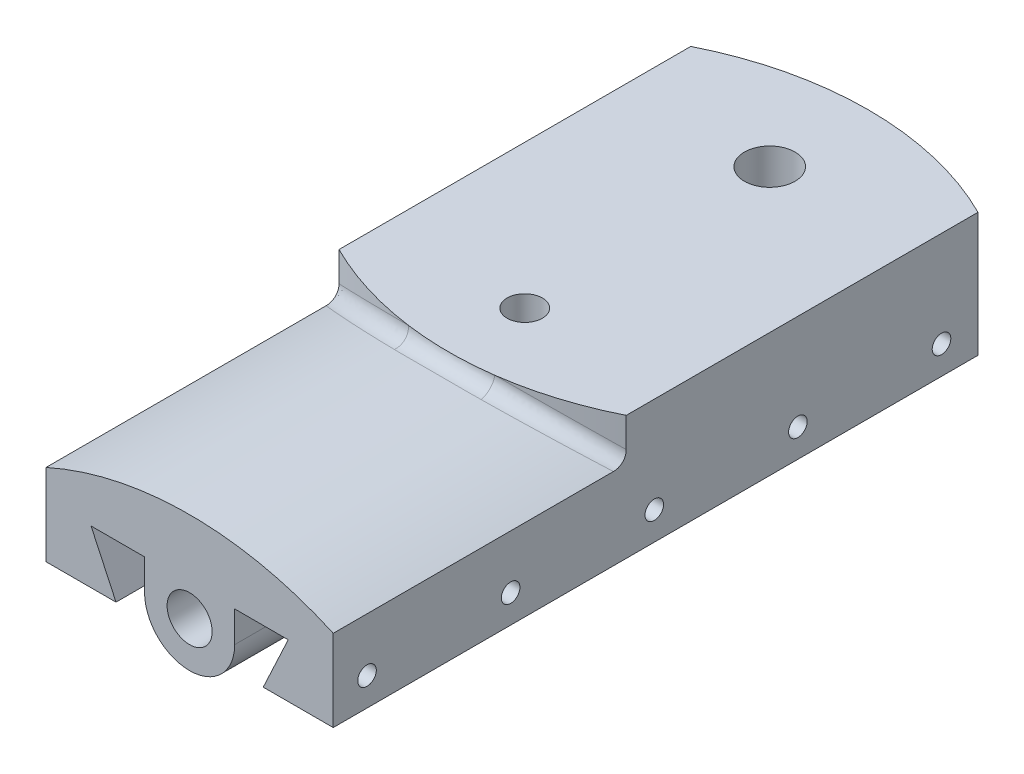
SolidWorks part; units mm, degrees
ref_plane "Ön Düzlem" through (0, 0, 0) normal (0, 0, 1) x (1, 0, 0)
ref_plane "Üst Düzlem" through (0, 0, 0) normal (0, 1, 0) x (1, 0, 0)
ref_plane "Sağ Düzlem" through (0, 0, 0) normal (1, 0, 0) x (0, 0, -1)
sketch "Çizim2" plane through (0, 0, 0) normal (0, 0, 1) x (1, 0, 0)
  line L0 (0, 0) -> (0, 44) construction
  line L1 (-51, 44) -> (51, 44)
  line L2 (51, 44) -> (51, 0)
  line L3 (51, 0) -> (26.1402, 0)
  line L4 (26.1402, 0) -> (35, 19)
  line L5 (35, 19) -> (16, 19)
  line L6 (16, 19) -> (16, 8)
  line L7 (0, 0) -> (0, -8) construction
  line L8 (-16, 19) -> (-16, 8)
  line L9 (-35, 19) -> (-16, 19)
  line L10 (-26.1402, 0) -> (-35, 19)
  line L11 (-51, 44) -> (-51, 0)
  line L12 (-51, 0) -> (-26.1402, 0)
  arc A0 (-16, 8) -> (16, 8) centre (0, 8) ccw
  circle A1 centre (0, 8) radius 8
  dimension "D8" = 16
  dimension "D1" = 44
  dimension "D2" = 51
  dimension "D3" = 35
  dimension "D4" = 65
  dimension "D5" = 19
  dimension "D6" = 16
  dimension "D7" = 11
extrude "Yükseklik-Ekstrüzyon1" add sketch "Çizim2" along normal mid plane 241
sketch "Çizim3" plane through (0, 0, 120.5) normal (0, 0, 1) x (1, 0, 0)
  line L0 (-51, 44) -> (-51, 0) construction
  line L1 (51, 0) -> (51, 44) construction
  line L2 (26.1402, 0) -> (51, 0) construction
  line L3 (-51, 0) -> (-26.1402, 0) construction
  line L4 (-51, 29) -> (-51, 44)
  line L5 (-51, 44) -> (51, 44)
  line L6 (51, 44) -> (51, 29)
  arc A0 (-51, 29) -> (51, 29) centre (0, -83.7273) cw
  point P11 (0, 40)
  dimension "D1" = 29
  dimension "D2" = 40
extrude "Kes-Ekstrüzyon2" cut sketch "Çizim3" against normal blind 92
sketch "Çizim4" plane through (0, 44, 0) normal (0, 1, 0) x (1, 0, 0)
  line L0 (0, 120.5) -> (0, 85.5) construction
  line L1 (51, 120.5) -> (-51, 120.5) construction
  line L2 (-51, -28.5) -> (-51, 0)
  line L3 (-51, -28.5) -> (-51, 120.5) construction
  line L4 (-51, -28.5) -> (24.9037, -28.5)
  line L5 (51, -28.5) -> (-51, -28.5) construction
  line L6 (24.9037, -28.5) -> (51, -28.5)
  line L7 (-51, -28.5) -> (51, -28.5) construction
  line L8 (51, -28.5) -> (51, -16.4559)
  line L9 (51, -28.5) -> (51, 120.5) construction
  circle A0 centre (0, 85.5) radius 114
  line M2 (-51, -28.5) -> (51, -28.5)
  line M3 (51, -28.5) -> (51, 120.5)
  dimension "D1" = 35
extrude "Kes-Ekstrüzyon3" cut sketch "Çizim4" against normal up to surface (15 mm away) contours A0 L4 M2 M3 | A0 L2 M2 region at (-38.3886, 44, 24.922) region at (38.3886, 44, 24.922) up to face at (0, 34.5, 74.5)
sketch "Çizim5" plane through (0, 0, 0) normal (0, 1, 0) x (1, 0, 0)
  line L0 (51, 120.5) -> (-51, 120.5) construction
  line L1 (0, 0) -> (0, 141.1531) construction
  line L3 (51, 120.5) -> (51, 108.4559)
  line L4 (0, 120.5) -> (51, 120.5)
  line L5 (-51, 120.5) -> (-51, 108.4559)
  line L7 (-51, 120.5) -> (51, 120.5)
  line L8 (51, 108.4559) -> (51, 120.5)
  line L9 (-51, 108.4559) -> (-51, 120.5)
  arc A0 (51, 108.4559) -> (-51, 108.4559) centre (0, 6.5) ccw
  arc A1 (-51, 108.4559) -> (51, 108.4559) centre (0, 6.5) cw
extrude "Kes-Ekstrüzyon4" cut sketch "Çizim5" along normal through all and the other way blind 26 contours A0 L7 L5 | A0 L3 L4 region at (-38.3886, 0, -116.922) region at (38.3886, 0, -116.922)
sketch "Çizim9" plane through (0, 0, 0) normal (1, 0, 0) x (0, 0, -1)
  line L0 (120.308, 12.5) -> (-76.5, 12.5)
  line L1 (120.308, 12.5) -> (120.5, -8)
  line L2 (-95.5, -8) -> (-95.5, 15.5)
  line L3 (-120.5, -8) -> (120.5, -8) construction
  line L4 (-95.5, 15.5) -> (-76.5, 15.5)
  line L5 (-76.5, 15.5) -> (-76.5, 12.5)
  line L6 (-95.5, -8) -> (120.5, -8)
  line L7 (-120.5, 0) -> (-120.5, 29) construction
  spline S0 degree 2 poles (120.5, -8) (119.3716, 0.0398) (119.3716, 8) knots 0 0 0 0.464738 0.464738 0.464738 weights 0.098 0.105436 0.112872 construction
  spline S1 degree 2 poles (120.5, 0) (119.9386, 8) (120.5, 16) knots 0 0 0 1 1 1 weights 0.106 0.114 0.122 construction
  dimension "D1" = 20.5
  dimension "D2" = 3
  dimension "D3" = 25
  dimension "D4" = 19
  dimension "D5" = 120.5
sketch "Çizim30" plane through (0, 0, 0) normal (1, 0, 0) x (0, 0, -1)
  line L0 (-66.6108, 22.5) -> (120.5, 22.5)
  line L1 (-66.6108, 22.5) -> (-76.5, 22.5)
  line L2 (-76.5, 22.5) -> (-76.5, 25.5)
  line L3 (-76.5, 25.5) -> (-95.5, 25.5)
  line L4 (-95.5, 25.5) -> (-95.5, -8)
  line L5 (-95.5, -8) -> (120.5, -8)
  line L6 (120.5, -8) -> (120.5, 22.5)
  line L7 (-120.5, 29) -> (-120.5, 0) construction
  line L8 (-120.5, -8) -> (120.5, -8) construction
  spline S0 degree 2 poles (120.5, -8) (119.3716, 0.0398) (119.3716, 8) knots 0 0 0 0.464738 0.464738 0.464738 weights 0.098 0.105436 0.112872 construction
  dimension "D1" = 25
  dimension "D2" = 120.5
  dimension "D3" = 19
  dimension "D4" = 3
  dimension "D5" = 30.5
extrude "Kes-Ekstrüzyon16" cut sketch "Çizim30" against normal mid plane 32
sketch "Çizim31" plane through (0, 0, 0) normal (0, 1, 0) x (1, 0, 0)
  line L0 (0, 120.5) -> (0, -156.6149) construction
  arc A0 (16, 119.3716) -> (-16, 119.3716) centre (0, 6.5) ccw construction
  point P7 (0, 85.5)
  point P8 (0, -1.5)
  point P10 (0, 85.5)
  dimension "D1" = 35
  dimension "D2" = 87
hole_wizard "M20x2.0 Dişli Delik3" positions "Çizim37" profile "Çizim38" tap size "M20x2.0" standard "ISO" end condition through all
sketch "Çizim37" plane through (0, 22.5, 0) normal (0, -1, 0) x (-1, 0, 0)
  point P0 (0, 85.5)
sketch "Çizim38" plane through (0, 22.5, -85.5) normal (1, 0, 0) x (0, 0, -1)
  line L0 (0, 0) -> (0, 21.5)
  line L1 (0, 21.5) -> (9, 21.5)
  line L2 (9, 21.5) -> (9, 0)
  line L5 (9, 0) -> (0, 0)
  line L11 (0, -6.35) -> (0, 107.95) construction
  dimension "Thru Tap Drill Dia." = 18
  dimension "Thru Tap Drill Depth" = 21.5
cosmetic thread "Delik Dişi7" parameters "D2"=20
hole_wizard "M14x1.5 Dişli Delik1" positions "Çizim41" profile "Çizim42" tap size "M14x1.5" standard "ISO" end condition through all
sketch "Çizim41" plane through (0, 22.5, 0) normal (0, -1, 0) x (-1, 0, 0)
  point P0 (0, -1.5)
  point P3 (0, -1.5)
  point P5 (0, -1.5)
sketch "Çizim42" plane through (0, 22.5, 1.5) normal (1, 0, 0) x (0, 0, -1)
  line L0 (0, 0) -> (0, 21.5)
  line L1 (0, 21.5) -> (6.25, 21.5)
  line L2 (6.25, 21.5) -> (6.25, 0)
  line L5 (6.25, 0) -> (0, 0)
  line L11 (0, -6.35) -> (0, 107.95) construction
  dimension "Thru Tap Drill Dia." = 12.5
  dimension "Thru Tap Drill Depth" = 21.5
cosmetic thread "Delik Dişi8" parameters "D2"=14
cosmetic thread "Delik Dişi10" parameters "D2"=14
fillet "Radyus1" radius 5 1 edges at (0, 40, 28.5)
sketch "Çizim43" plane through (0, 0, 0) normal (1, 0, 0) x (0, 0, -1)
  line L0 (120.5, 0) -> (-156.6149, 0) construction
  line L1 (-120.5, 0) -> (-120.5, 29) construction
  point P0 (-108.5, 10)
  dimension "D1" = 10
  dimension "D2" = 12
sketch "Çizim44" plane through (51, 0, 0) normal (1, 0, 0) x (0, 0, -1)
  point P0 (-108.5, 10)
hole_wizard "M6 Boşluklu Delik1" positions "Çizim44" profile "Çizim45" hole size "M6" standard "ISO"
sketch "Çizim45" plane through (51, 10, 108.5) normal (0, 1, 0) x (0, 0, -1)
  line L0 (0, 0) -> (0, 17.1796)
  line L1 (0, 17.1796) -> (3.3, 15.1968)
  line L2 (3.3, 15.1968) -> (3.3, 0)
  line L5 (3.3, 0) -> (0, 0)
  line L10 (0, 17.1796) -> (-3.3, 15.1968) construction
  line L11 (0, -6.35) -> (0, 107.95) construction
  dimension "Hole Dia." = 6.6
  dimension "Hole Depth" = 15.1968
  dimension "Drill Angle" = 118
pattern_linear "LÇoğaltma1" count 5 spacing 51 along (0, 0, -1) of "M6 Boşluklu Delik1"
extrude "Kes-Ekstrüzyon9" cut sketch "Çizim9" against normal mid plane 32 rebuild error yes
sketch "Çizim12" plane through (0, 0, 0) normal (0, 0, 1) x (1, 0, 0)
  line L0 (-4.472, 1.3667) -> (-5.1116, -12.3044)
  line L1 (-5.1116, -12.3044) -> (4.472, -12.3044)
  line L2 (4.472, -12.3044) -> (4.472, 1.3667)
  arc A0 (-4.472, 1.3667) -> (4.472, 1.3667) centre (0, 8) ccw
extrude "Kes-Ekstrüzyon12" cut sketch "Çizim12" against normal blind 138 rebuild error yes
